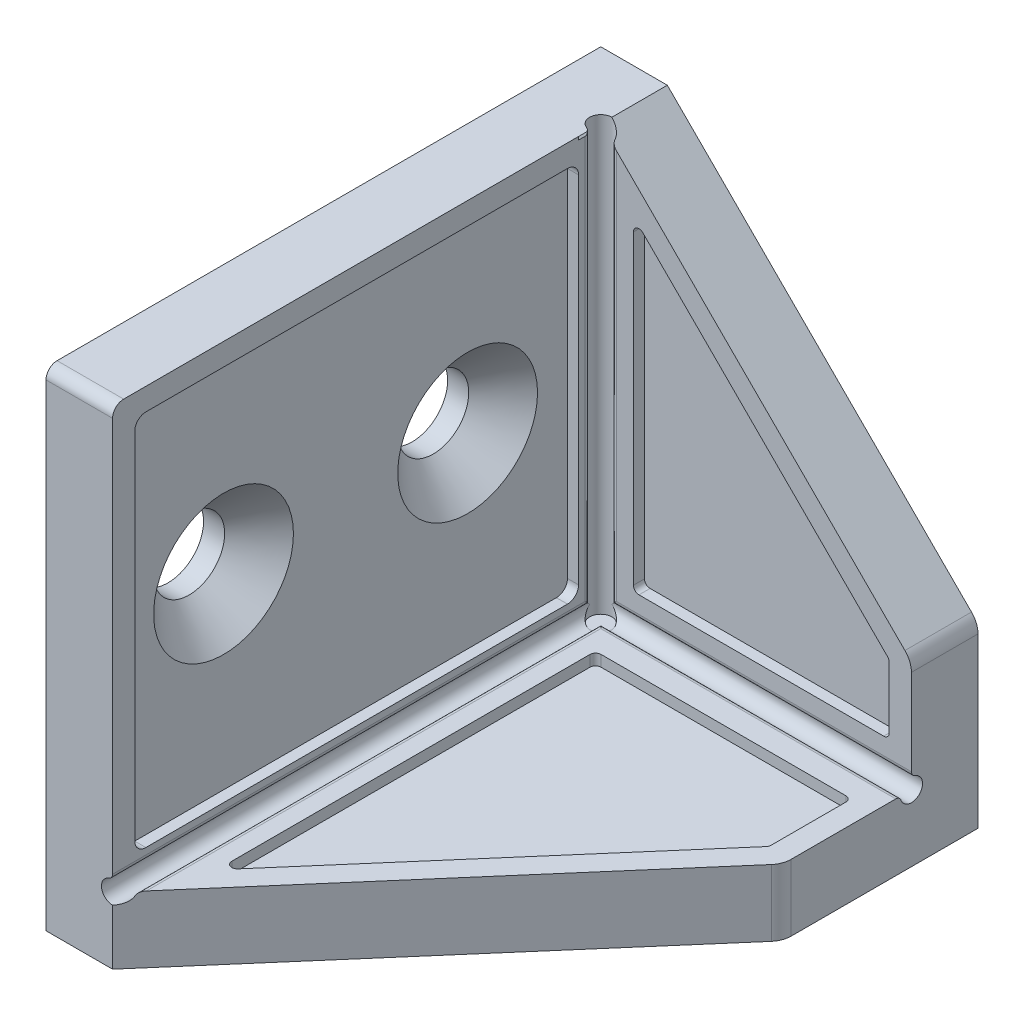
SolidWorks part; units mm, degrees
material "Polyester Resin"
ref_plane "Front Plane" through (0, 0, 0) normal (0, 0, 1) x (1, 0, 0)
ref_plane "Top Plane" through (0, 0, 0) normal (0, 1, 0) x (1, 0, 0)
ref_plane "Right Plane" through (0, 0, 0) normal (1, 0, 0) x (0, 0, -1)
sketch "Sketch1" plane through (0, 0, 0) normal (0, 0, 1) x (1, 0, 0)
  line L0 (0, 24.3075) -> (0, -0.6925)
  line L1 (0, -0.6925) -> (25, -0.6925)
  line L2 (0, 24.3075) -> (25, -0.6925)
  dimension "D1" = 25
  dimension "D2" = 25
extrude "Boss-Extrude2" add sketch "Sketch1" along normal blind 25
sketch "Sketch2" plane through (0, 0, 25) normal (0, 0, 1) x (1, 0, 0)
  line L0 (3, 21.3075) -> (3, 2.3075)
  line L1 (25, -0.6925) -> (0, 24.3075) construction
  line L2 (3, 2.3075) -> (22, 2.3075)
  line L3 (0, 24.3075) -> (0, -0.6925) construction
  line L4 (0, -0.6925) -> (25, -0.6925) construction
  line L5 (3, 21.3075) -> (22, 2.3075)
  dimension "D1" = 3
  dimension "D2" = 3
extrude "Cut-Extrude1" cut sketch "Sketch2" against normal blind 21
sketch "Sketch3" plane through (12.1537, 12.1537, 0) normal (0.7071, 0.7071, 0) x (0.7071, -0.7071, 0)
  line L0 (-12.9453, -4) -> (13.9247, -4)
  line L4 (13.9247, -4) -> (13.9247, -3)
  line L5 (13.9247, -3) -> (-12.9453, -3)
  line L6 (-12.9453, -3) -> (-12.9453, -4)
extrude "Cut-Extrude3" cut sketch "Sketch3" against normal blind 0.1
sketch "Sketch4" plane through (0, 0, 4) normal (0, 0, 1) x (1, 0, 0)
  line L0 (3, 21.3075) -> (3, 2.3075)
  line L1 (3, 2.3075) -> (22, 2.3075)
  line L2 (22, 2.3075) -> (3, 21.3075)
extrude "Cut-Extrude4" cut sketch "Sketch4" against normal up to surface (1 mm away) up to face at (12.4646, 11.7721, 3)
sketch "Sketch5" plane through (0, 0, 3) normal (0, 0, 1) x (1, 0, 0)
  line L0 (22, 2.3075) -> (21.8586, 2.3075)
  line L1 (21.8586, 2.3075) -> (21.9293, 2.2368)
  line L2 (21.9293, 2.2368) -> (22, 2.3075)
extrude "Boss-Extrude3" add sketch "Sketch5" along normal up to surface (1 mm away) up to face at (21.9293, 2.2839, 4)
sketch "Sketch6" plane through (0, 2.3075, 0) normal (0, 1, 0) x (1, 0, 0)
  line L0 (22, -3) -> (3, -3) construction
  line L1 (3, -3) -> (3, -25) construction
  line L2 (3, -25) -> (22, -25)
  point P4 (0, 0)
sketch "Sketch8" plane through (3, 0, 0) normal (1, 0, 0) x (0, 0, -1)
  line L0 (-25, 2.3075) -> (-25, 21.3075) construction
  line L1 (-25, 21.3075) -> (-3, 21.3075) construction
  line L2 (-25, 21.3075) -> (-14, 21.3075)
  line L3 (-14, 21.3075) -> (-3, 21.3075)
  line L4 (-3, 21.3075) -> (-3, 11.7368)
  line L5 (-3, 21.166) -> (-3, 2.3075) construction
  line L6 (-3, 11.7368) -> (-3, 2.3075)
  circle A0 centre (-8.5, 11.7368) radius 1.5
  circle A1 centre (-19.5, 11.7368) radius 1.5
  dimension "D1" = 3
  dimension "D2" = 3
extrude "Cut-Extrude5" cut sketch "Sketch8" against normal blind 18 and the other way blind 15 contours A0 | A1 region at (3, 11.7368, 8.5) region at (3, 11.7368, 19.5)
sketch "Sketch9" plane through (3, 0, 0) normal (1, 0, 0) x (0, 0, -1)
  circle A0 centre (-19.5, 11.7368) radius 3
  circle A1 centre (-8.5, 11.7368) radius 3
  dimension "D1" = 6
  dimension "D2" = 6
sketch "Sketch10" plane through (3, 0, 0) normal (1, 0, 0) x (0, 0, -1)
  line L0 (-25, 21.3075) -> (-25, 2.3075) construction
  line L1 (-24, 20.3075) -> (-4, 20.3075)
  line L2 (-24, 20.3075) -> (-24, 3.3075)
  line L3 (-24, 3.3075) -> (-4, 3.3075)
  line L4 (-4, 20.3075) -> (-4, 3.3075)
  line L5 (-4, 21.3075) -> (-25, 21.3075) construction
  line L6 (-3, 2.3075) -> (-25, 2.3075) construction
  line L7 (-3, 21.166) -> (-3, 2.3075) construction
  dimension "D1" = 1
  dimension "D2" = 1
  dimension "D3" = 1
  dimension "D4" = 1
extrude "Cut-Extrude7" cut sketch "Sketch10" against normal blind 0.5
sketch "Sketch12" plane through (0, 0, 25) normal (0, 0, 1) x (1, 0, 0)
  line L0 (3, 21.3075) -> (0, 21.3075)
  line L1 (0, 24.3075) -> (0, -0.6925) construction
  line L2 (0, 21.3075) -> (0, 24.3075)
  line L3 (0, 24.3075) -> (3, 21.3075)
  line L4 (22, 2.3075) -> (22, -0.6925)
  line L5 (0, -0.6925) -> (25, -0.6925) construction
  line L6 (22, -0.6925) -> (25, -0.6925)
  line L7 (25, -0.6925) -> (22, 2.3075)
extrude "Cut-Extrude9" cut sketch "Sketch12" against normal through all
fillet "Fillet1" radius 0.5 1 edges at (1.5, 21.3075, 25)
fillet "Fillet2" radius 0.5 1 edges at (2.75, 20.3075, 24)
fillet "Fillet3" radius 0.5 3 edges at (2.75, 3.3075, 24) (2.75, 3.3075, 4) (2.75, 20.3075, 4)
sketch "Sketch13" plane through (0, 2.3075, 0) normal (0, 1, 0) x (1, 0, 0)
  line L0 (22, -3) -> (3, -25)
  line L1 (3, -25) -> (22, -25)
  line L2 (22, -25) -> (22, -3)
extrude "Cut-Extrude10" cut sketch "Sketch13" against normal through all
sketch "Sketch14" plane through (0, -0.6925, 0) normal (0, -1, 0) x (1, 0, 0)
  line L0 (22, 3) -> (3, 25) construction
  line L1 (22, 0) -> (17, 0)
  line L2 (22, 0) -> (22, 8.7895)
  line L3 (22, 8.7895) -> (17, 8.7895)
  line L4 (17, 0) -> (17, 8.7895)
  dimension "D1" = 5
extrude "Cut-Extrude11" cut sketch "Sketch14" against normal through all
sketch "Sketch15" plane through (0, -0.6925, 0) normal (0, -1, 0) x (1, 0, 0)
  line L0 (1, 24) -> (2.5423, 24)
  line L1 (2.5423, 24) -> (9.2712, 16.2087)
  line L2 (16, 8.4174) -> (16, 1)
  line L3 (16, 1) -> (1, 1)
  line L4 (1, 1) -> (1, 7.7441)
  line L5 (17, 8.7895) -> (3, 25) construction
  line L6 (0, 25) -> (0, 0) construction
  line L7 (0, 0) -> (17, 0) construction
  line L8 (17, 8.7895) -> (17, 0) construction
  line L9 (0, 25) -> (3, 25) construction
  line L10 (9.2712, 16.2087) -> (1, 9.0654)
  line L12 (1, 7.7441) -> (9.9248, 15.4519)
  line L13 (9.9248, 15.4519) -> (16, 8.4174)
  line L14 (1, 9.0654) -> (1, 24)
  dimension "D1" = 1
  dimension "D2" = 1
  dimension "D3" = 1
  dimension "D4" = 1
  dimension "D5" = 1
  dimension "D6" = 1
extrude "Cut-Extrude12" cut sketch "Sketch15" against normal blind 0.5
fillet "Fillet5" radius 0.5 9 edges at (1, -0.4425, 7.7441) (1, -0.4425, 1) (16, -0.4425, 1) (16, -0.4425, 8.4174) (2.5423, -0.4425, 24) (1, -0.4425, 24) (1, -0.4425, 9.0654) (9.2712, -0.4425, 16.2087) (9.9248, -0.4425, 15.4519)
sketch "Sketch16" plane through (0, 0, 0) normal (0, 0, -1) x (-1, 0, 0)
  line L0 (-1, 0.3075) -> (-1, 3.8933)
  line L1 (-1, 20.3075) -> (-2.5858, 20.3075)
  line L2 (-2.5858, 20.3075) -> (-9.2929, 13.6004)
  line L3 (-16, 6.8933) -> (-16, 0.3075)
  line L4 (-16, 0.3075) -> (-1, 0.3075)
  line L5 (-17, 7.3075) -> (-3, 21.3075) construction
  line L6 (0, 21.3075) -> (0, -0.6925) construction
  line L7 (0, -0.6925) -> (-17, -0.6925) construction
  line L8 (-17, 7.3075) -> (-17, -0.6925) construction
  line L9 (0, 21.3075) -> (-3, 21.3075) construction
  line L10 (-9.2929, 13.6004) -> (-1, 5.3075)
  line L12 (-1, 3.8933) -> (-10, 12.8933)
  line L13 (-10, 12.8933) -> (-16, 6.8933)
  line L14 (-1, 5.3075) -> (-1, 20.3075)
  point P19 (-5.1464, 9.4539)
  dimension "D1" = 1
  dimension "D2" = 1
  dimension "D3" = 1
  dimension "D4" = 1
  dimension "D5" = 1
  dimension "D6" = 1
extrude "Cut-Extrude13" cut sketch "Sketch16" against normal blind 0.5
fillet "Fillet7" radius 0.25 9 edges at (1, 3.8933, 0.25) (1, 20.3075, 0.25) (16, 6.8933, 0.25) (16, 0.3075, 0.25) (1, 0.3075, 0.25) (1, 5.3075, 0.25) (9.2929, 13.6004, 0.25) (2.5858, 20.3075, 0.25) (10, 12.8933, 0.25)
fillet "Fillet10" radius 1 2 edges at (17, 0.8075, 8.7895) (17, 7.3075, 1.5)
hole_wizard "CSK for M3 Flat Head Machine Screw1" positions "Sketch17" profile "Sketch18" countersink size "M3" standard "ANSI Metric" end condition through all
sketch "Sketch17" plane through (2.5, 0, 0) normal (1, 0, 0) x (0, 0, -1)
  point P0 (-19.5, 11.7368)
  point P3 (-8.5, 11.7368)
sketch "Sketch18" plane through (2.5, 11.7368, 19.5) normal (0, 1, 0) x (0, 0, -1)
  line L0 (0, 0) -> (0, 2.5)
  line L1 (0, 2.5) -> (1.6, 2.5)
  line L2 (1.6, 2.5) -> (1.6, 1.55)
  line L3 (1.6, 1.55) -> (3.15, 0)
  line L5 (3.15, 0) -> (0, 0)
  line L6 (-1.6, 1.55) -> (-3.15, 0) construction
  line L11 (0, -6.35) -> (0, 107.95) construction
  dimension "Thru Hole Dia." = 3.2
  dimension "Thru Hole Depth" = 2.5
  dimension "Near C'Sink Dia." = 6.3
  dimension "Near C'Sink Angle" = 90
sketch "Sketch19" plane through (17, 0, 0) normal (1, 0, 0) x (0, 0, -1)
  circle A0 centre (-3, 2.3075) radius 0.5
  dimension "D1" = 1
extrude "Cut-Extrude14" cut sketch "Sketch19" against normal blind 14
sketch "Sketch20" plane through (0, 0, 25) normal (0, 0, 1) x (1, 0, 0)
  circle A0 centre (3, 2.3075) radius 0.5
  dimension "D1" = 1
extrude "Cut-Extrude15" cut sketch "Sketch20" against normal blind 22
sketch "Sketch21" plane through (0, 21.3075, 0) normal (0, 1, 0) x (1, 0, 0)
  circle A0 centre (3, -3) radius 0.5
  dimension "D1" = 1
extrude "Cut-Extrude16" cut sketch "Sketch21" against normal blind 19.5
fillet "Fillet11" radius 0.25 6 edges at (3, 11.9868, 3.5) (3, 2.8075, 14.25) (3.5, 11.8075, 3) (10.25, 2.8075, 3) (10.25, 2.3075, 3.5) (3.5, 2.3075, 13.9605)
sketch "Sketch22" plane through (0, 2.3075, 0) normal (0, 1, 0) x (1, 0, 0)
  line L0 (4.4714, -21.7663) -> (16, -8.4174)
  line L1 (4.4714, -4.7071) -> (16, -4.7071)
  line L2 (4.4714, -4.7071) -> (4.4714, -21.7663)
  line L4 (16, -4.7071) -> (16, -8.4174)
  line L5 (16.7568, -9.071) -> (3.7071, -24.1812) construction
  line L6 (17, -8.4174) -> (17, -3.7071) construction
  line L7 (17, -3.7071) -> (3.7071, -3.7071) construction
  line L8 (3.4714, -24.4542) -> (3.4714, -3.4714) construction
  dimension "D1" = 1
  dimension "D2" = 1
  dimension "D3" = 1
  dimension "D4" = 1
extrude "Cut-Extrude17" cut sketch "Sketch22" against normal blind 0.5
fillet "Fillet12" radius 0.25 3 edges at (16, 2.0575, 8.4174) (16, 2.0575, 4.7071) (4.4714, 2.0575, 4.7071)
fillet "Fillet13" radius 0.25 1 edges at (4.4714, 2.0575, 21.7663)
sketch "Sketch23" plane through (0, 0, 3) normal (0, 0, 1) x (1, 0, 0)
  line L0 (4.4714, 18.4218) -> (16, 6.8933)
  line L1 (16, 6.8933) -> (16, 3.7789)
  line L2 (16, 3.7789) -> (4.4714, 3.7789)
  line L3 (4.4714, 3.7789) -> (4.4714, 18.4218)
  line L4 (16.7071, 7.6004) -> (3.7071, 20.6004) construction
  line L5 (17, 3.0146) -> (17, 6.8933) construction
  line L6 (17, 2.7789) -> (3.4714, 2.7789) construction
  line L7 (3.4714, 2.7789) -> (3.4714, 20.8361) construction
  dimension "D1" = 1
  dimension "D2" = 1
  dimension "D3" = 1
  dimension "D4" = 1
extrude "Cut-Extrude18" cut sketch "Sketch23" against normal blind 0.5
fillet "Fillet14" radius 0.25 3 edges at (4.4714, 18.4218, 2.75) (16, 3.7789, 2.75) (4.4714, 3.7789, 2.75)
fillet "Fillet15" radius 0.25 1 edges at (16, 6.8933, 2.75)
